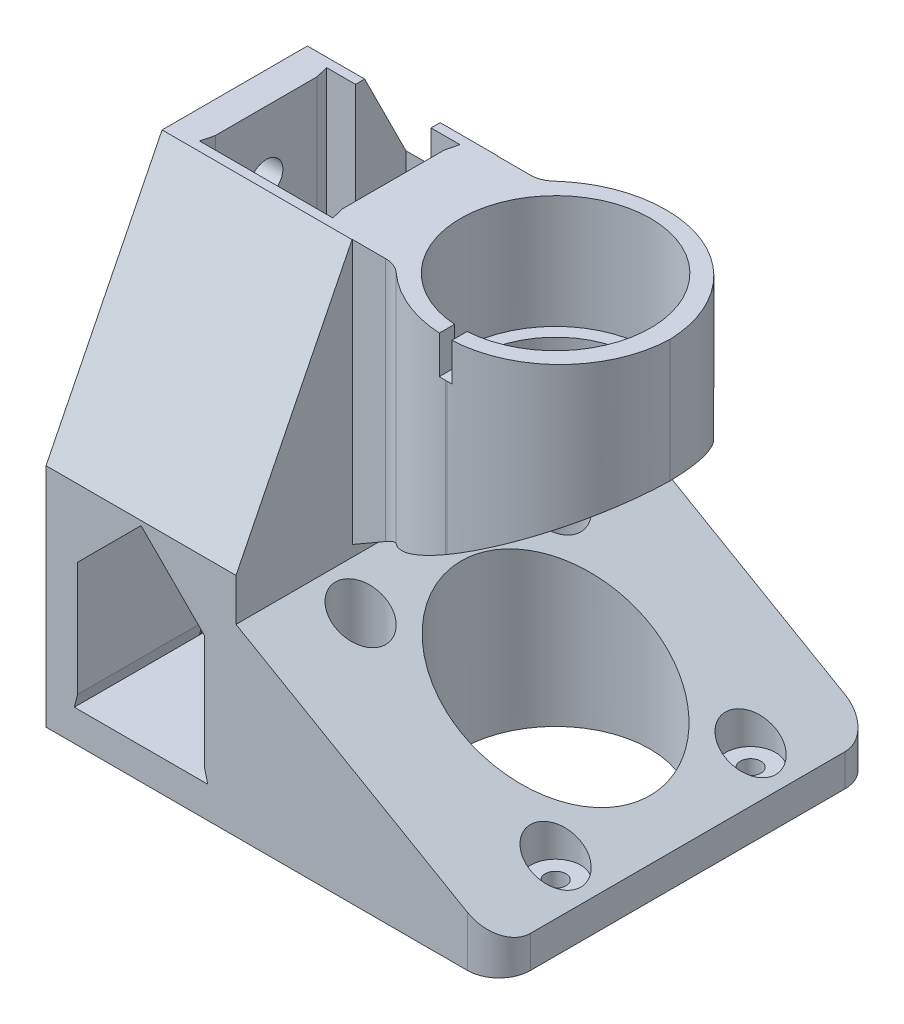
SolidWorks part; units mm, degrees
ref_plane "Front Plane" through (0, 0, 0) normal (0, 0, 1) x (1, 0, 0)
ref_plane "Top Plane" through (0, 0, 0) normal (0, 1, 0) x (1, 0, 0)
ref_plane "Right Plane" through (0, 0, 0) normal (1, 0, 0) x (0, 0, -1)
sketch "Sketch1" plane through (0, 0, 0) normal (0, 1, 0) x (1, 0, 0)
  line L1 (0, 0) -> (72, 0)
  line L2 (0, 0) -> (0, 60)
  line L3 (0, 60) -> (72, 60)
  line L4 (72, 0) -> (72, 60)
  dimension "D1" = 72
  dimension "D2" = 60
extrude "Boss-Extrude1" add sketch "Sketch1" along normal blind 5
sketch "Sketch2" plane through (0, 5, 0) normal (0, 1, 0) x (1, 0, 0)
  line L0 (0, 0) -> (72, 0) construction
  line L1 (0, 60) -> (5, 60)
  line L2 (0, 60) -> (0, 0)
  line L3 (0, 0) -> (5, 0)
  line L4 (5, 60) -> (5, 0)
  dimension "D1" = 5
extrude "Boss-Extrude2" add sketch "Sketch2" along normal blind 68
sketch "Sketch3" plane through (0, 5, 0) normal (0, 1, 0) x (1, 0, 0)
  line L0 (72, 60) -> (5, 60) construction
  line L1 (25.2, 60) -> (30.2, 60)
  line L2 (25.2, 60) -> (25.2, 0)
  line L3 (25.2, 0) -> (30.2, 0)
  line L4 (30.2, 60) -> (30.2, 0)
  line L5 (5, 0) -> (72, 0) construction
  line L6 (5, 0) -> (5, 60) construction
  dimension "D1" = 5
  dimension "D2" = 20.2
extrude "Boss-Extrude3" add sketch "Sketch3" along normal blind 68
sketch "Sketch11" plane through (0, 0, -60) normal (0, 0, -1) x (-1, 0, 0)
  line L0 (-25.2, 25.2) -> (-15.1, 35.3)
  line L1 (-25.2, 73) -> (-25.2, 5) construction
  line L2 (-15.1, 35.3) -> (-5, 25.2)
  line L3 (-5, 73) -> (-5, 5) construction
  line L4 (-5, 25.2) -> (-5, 73)
  line L5 (-5, 73) -> (-25.2, 73)
  line L6 (-25.2, 73) -> (-25.2, 25.2)
  line L7 (-25.2, 5) -> (-5, 5) construction
  dimension "D1" = 20.2
  dimension "D2" = 20.2
  dimension "D3" = 45
  dimension "D4" = 45
extrude "Boss-Extrude4" add sketch "Sketch11" against normal up to surface (60 mm away) up to face at (26.48, 31.2, 0)
chamfer "Chamfer1" distance 42 angle 30 1 edges at (30.2, 5, -30) first distance on face at (51.1, 5, -30)
sketch "Sketch12" plane through (0, 73, 0) normal (0, 1, 0) x (1, 0, 0)
  line L0 (0, 30) -> (30.2, 30) construction
  line L1 (5, 40.1) -> (25.2, 40.1)
  line L2 (5, 40.1) -> (5, 19.9)
  line L3 (5, 19.9) -> (25.2, 19.9)
  line L4 (25.2, 40.1) -> (25.2, 19.9)
  line L5 (5, 40.1) -> (25.2, 19.9) construction
  line L6 (5, 19.9) -> (25.2, 40.1) construction
  line L8 (30.2, 0) -> (30.2, 60) construction
  line L9 (0, 60) -> (0, 0) construction
  point P0 (15.1, 30)
  point P8 (15.2, 30)
  point P9 (15.1, 30)
  dimension "D1" = 20.2
  dimension "D2" = 20.2
  dimension "D3" = 5
extrude "Cut-Extrude8" cut sketch "Sketch12" against normal up to surface (68 mm away) up to face at (15.1, 5, -30)
sketch "Sketch5" plane through (0, 5, 0) normal (0, 1, 0) x (1, 0, 0)
  line L0 (72, 0) -> (72, 60) construction
  line L1 (5, 0) -> (25.2, 0) construction
  circle A0 centre (51, 30) radius 15
  dimension "D1" = 30
  dimension "D2" = 21
  dimension "D3" = 30
extrude "Cut-Extrude1" cut sketch "Sketch5" against normal through all both and the other way through all
sketch "Sketch8" plane through (5, 0, 0) normal (1, 0, 0) x (0, 0, -1)
  line L0 (0, 73) -> (60, 73) construction
  line L1 (30, 73) -> (30, 29.2487) construction
  line L2 (0, 29.2487) -> (60, 29.2487) construction
  circle A0 centre (30, 63) radius 2.65
  dimension "D1" = 5.3
  dimension "D2" = 10
extrude "Cut-Extrude5" cut sketch "Sketch8" against normal blind 10
sketch "Sketch9" plane through (0, 0, 0) normal (0, -1, 0) x (1, 0, 0)
  line L1 (0, -60) -> (0, 0) construction
  line L2 (0, -30) -> (72, -30) construction
  line L3 (72, 0) -> (72, -60) construction
  circle A0 centre (15, -30) radius 2.65
  dimension "5.3" = 5.3
  dimension "D2" = 15
extrude "Cut-Extrude6" cut sketch "Sketch9" against normal through all both and the other way through all contours A0
fillet "Fillet1" radius 5 2 edges at (72, 2.5577, -60) (72, 2.5577, 0)
sketch "Sketch10" plane through (0, 0, 0) normal (-1, 0, 0) x (0, 0, 1)
  line L0 (-60, 0) -> (0, 0) construction
  line L1 (0, 73) -> (0, 0) construction
  circle A0 centre (-30, 15) radius 2.65
  dimension "D3" = 5.3
  dimension "D1" = 15
  dimension "D2" = 30
extrude "Cut-Extrude7" cut sketch "Sketch10" against normal blind 10
sketch "Sketch13" plane through (0, 0, 0) normal (0, 0, 1) x (1, 0, 0)
  line L0 (5, 5) -> (4.5, 5)
  line L1 (4.5, 5) -> (5, 7)
  line L2 (5, 7) -> (5, 5)
  line L3 (25.2, 5) -> (25.7, 5)
  line L4 (25.7, 5) -> (25.2, 7)
  line L5 (25.2, 25.2) -> (25.2, 5) construction
  line L6 (25.2, 7) -> (25.2, 5)
  dimension "D1" = 2
  dimension "D2" = 2
  dimension "D3" = 0.5
  dimension "D4" = 0.5
extrude "Cut-Extrude9" cut sketch "Sketch13" against normal through all both and the other way through all
sketch "Sketch14" plane through (0, 73, 0) normal (0, 1, 0) x (1, 0, 0)
  line L0 (15.1, 44.9993) -> (15.1, 15.0007) construction
  line L3 (25.2, 40.1) -> (5, 40.1) construction
  line L4 (9.1, 40.1) -> (21.1, 40.1)
  line L5 (9.1, 40.1) -> (9.1, 48.1)
  line L6 (9.1, 48.1) -> (21.1, 48.1)
  line L7 (21.1, 40.1) -> (21.1, 48.1)
  line L8 (15.1, 48.1) -> (15.1, 40.1) construction
  line L14 (25.2, 19.9) -> (25.7, 19.9)
  line L15 (25.7, 19.9) -> (25.2, 21.9)
  line L16 (25.2, 19.9) -> (25.2, 40.1) construction
  line L17 (25.2, 21.9) -> (25.2, 19.9)
  line L18 (5, 19.9) -> (4.5, 19.9)
  line L19 (4.5, 19.9) -> (5, 21.9)
  line L20 (5, 40.1) -> (5, 19.9) construction
  line L21 (5, 21.9) -> (5, 19.9)
  line L22 (25.2, 40.1) -> (25.7, 40.1)
  line L23 (25.7, 40.1) -> (25.2, 38.1)
  line L24 (25.2, 38.1) -> (25.2, 40.1)
  line L25 (5, 40.1) -> (4.5, 40.1)
  line L26 (4.5, 40.1) -> (5, 38.1)
  line L27 (5, 38.1) -> (5, 40.1)
  dimension "D1" = 8
  dimension "D2" = 12
  dimension "D3" = 2
  dimension "D4" = 0.5
  dimension "D5" = 2
  dimension "D6" = 0.5
  dimension "D7" = 2
  dimension "D8" = 0.5
  dimension "D9" = 0.5
  dimension "D10" = 2
extrude "Cut-Extrude10" cut sketch "Sketch14" against normal up to surface (68 mm away) up to face at (15, 5, -32.65)
ref_plane "Bearing Base Plane" through (0, 55, 0) normal (0, 1, 0) x (1, 0, 0)
sketch "Sketch15" plane through (30.2, 0, 0) normal (1, 0, 0) x (0, 0, -1)
  line L1 (12.5, 53.5) -> (47.5, 53.5)
  line L2 (12.5, 53.5) -> (12.5, 73)
  line L3 (12.5, 73) -> (47.5, 73)
  line L4 (47.5, 53.5) -> (47.5, 73)
  line L7 (0, 73) -> (60, 73) construction
  line L8 (33, 55) -> (-33, 55) construction
  point P21 (30, 73)
  dimension "D1" = 35
  dimension "D2" = 1.5
extrude "Boss-Extrude5" add sketch "Sketch15" along normal blind 39
sketch "Sketch16" plane through (0, 55, 0) normal (0, -1, 0) x (1, 0, 0)
  circle A0 centre (51, -30) radius 15.1
  dimension "D1" = 30.2
extrude "Cut-Extrude11" cut sketch "Sketch16" against normal through all
sketch "Sketch17" plane through (0, 53.5, 0) normal (0, -1, 0) x (1, 0, 0)
  circle A0 centre (51, -30) radius 13
  dimension "D1" = 26
extrude "Cut-Extrude12" cut sketch "Sketch17" against normal through all
fillet "Fillet2" radius 18 2 edges at (69.2, 63.25, -47.5) (69.2, 63.25, -12.5)
chamfer "Chamfer2" distance 22.5 angle 60 1 edges at (30.2, 53.5, -30) first distance on face at (30.2, 57.1872, -30)
sketch "Sketch6" plane through (0, 0, 0) normal (0, -1, 0) x (1, 0, 0)
  line L1 (35.5, -14.5) -> (66.5, -14.5) construction
  line L2 (35.5, -14.5) -> (35.5, -45.5) construction
  line L3 (35.5, -45.5) -> (66.5, -45.5) construction
  line L4 (66.5, -14.5) -> (66.5, -45.5) construction
  line L5 (35.5, -14.5) -> (66.5, -45.5) construction
  line L6 (35.5, -45.5) -> (66.5, -14.5) construction
  circle A0 centre (66.5, -14.5) radius 1.65
  circle A1 centre (66.5, -45.5) radius 1.65
  circle A2 centre (35.5, -45.5) radius 1.65
  circle A3 centre (35.5, -14.5) radius 1.65
  point P0 (51, -30)
  dimension "D3" = 3.3
  dimension "D1" = 31
  dimension "D2" = 31
extrude "Cut-Extrude2" cut sketch "Sketch6" against normal through all
sketch "Sketch7" plane through (0, 5, 0) normal (0, 1, 0) x (1, 0, 0)
  circle A0 centre (66.5, 45.5) radius 4
  circle A1 centre (66.5, 14.5) radius 4
  circle A2 centre (35.5, 14.5) radius 4
  circle A4 centre (35.5, 45.5) radius 4
  dimension "D1" = 8
extrude "Cut-Extrude4" cut sketch "Sketch7" along normal through all
sketch "Sketch18" plane through (0, 73, 0) normal (0, 1, 0) x (1, 0, 0)
  line L0 (51, 52.2266) -> (51, 7.7734) construction
  line L5 (52, 22.5) -> (50, 22.5)
  line L6 (52, 22.5) -> (52, 7.5)
  line L7 (52, 7.5) -> (50, 7.5)
  line L8 (50, 22.5) -> (50, 7.5)
  line L9 (52, 22.5) -> (50, 7.5) construction
  line L10 (52, 7.5) -> (50, 22.5) construction
  line L11 (51, 22.5) -> (51, 7.5) construction
  circle A0 centre (51, 30) radius 15 construction
  point P0 (51, 15)
  point P10 (51, 30)
  dimension "D1" = 2
  dimension "D2" = 15
extrude "Cut-Extrude13" cut sketch "Sketch18" against normal blind 6
chamfer "Chamfer3" distance 37 angle 26.5 2 edges at (15.1, 73, 0) (15.1, 73, -60) first distance on face at (15.0286, 18.2714, 0) first distance on face at (15.1, 15.6714, -60)
sketch "Sketch19" plane through (0, 73, 0) normal (0, 1, 0) x (1, 0, 0)
  line L0 (30.2, 60) -> (30.2, 47.5) construction
  line L1 (30.2, 51.5) -> (35.5, 51.5)
  line L2 (30.2, 51.5) -> (30.2, 41.5)
  line L3 (30.2, 41.5) -> (35.5, 41.5)
  line L4 (35.5, 51.5) -> (35.5, 41.5)
  line L5 (30.2, 12.5) -> (30.2, 0) construction
  line L6 (30.2, 8.5) -> (35.5, 8.5)
  line L7 (30.2, 8.5) -> (30.2, 18.5)
  line L8 (30.2, 18.5) -> (35.5, 18.5)
  line L9 (35.5, 8.5) -> (35.5, 18.5)
  arc A0 (34.8542, 41.5525) -> (38.9641, 47.5) centre (35.5, 45.5) ccw construction
  circle A1 centre (35.5, 45.5) radius 4 construction
  arc A2 (38.9641, 12.5) -> (34.8542, 18.4475) centre (35.5, 14.5) ccw construction
  circle A3 centre (35.5, 14.5) radius 4 construction
  dimension "D1" = 10
  dimension "D2" = 5.3
  dimension "D3" = 5.3
  dimension "D4" = 10
extrude "Cut-Extrude14" cut sketch "Sketch19" against normal up to surface (46.8112 mm away) up to face at (39.5, 23.8794, -45.5)
fillet "Fillet3" radius 19 2 edges at (38.9641, 54.53, -47.5) (38.9641, 54.53, -12.5)
mirror "Mirror1" [suppressed] of bodies 114
delete or keep bodies "Body-Delete/Keep 1" [suppressed] type delete bodies bodies 114
